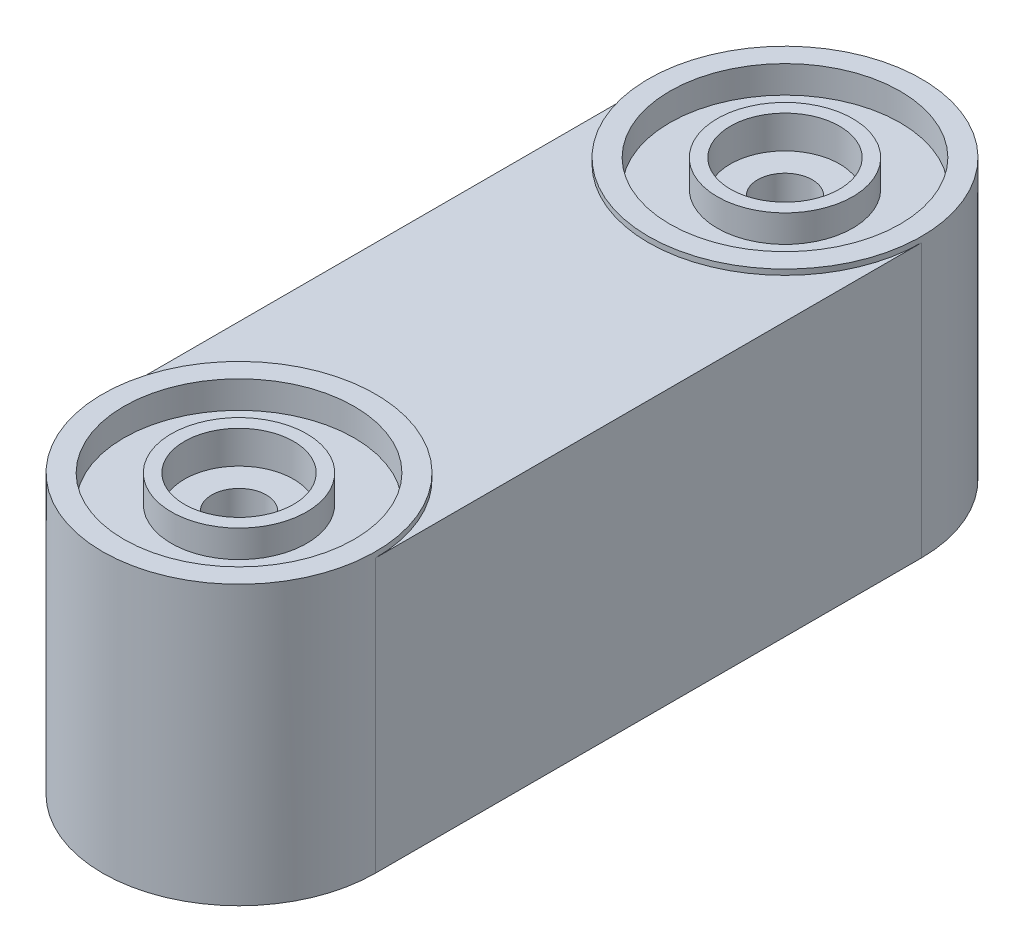
SolidWorks part; units mm, degrees
ref_plane "Ebene vorne" through (0, 0, 0) normal (0, 0, 1) x (1, 0, 0)
ref_plane "Ebene oben" through (0, 0, 0) normal (0, 1, 0) x (1, 0, 0)
ref_plane "Ebene rechts" through (0, 0, 0) normal (1, 0, 0) x (0, 0, -1)
sketch "Skizze1" plane through (0, 0, 0) normal (0, 0, 1) x (1, 0, 0)
  line L1 (-25, -25) -> (25, -25)
  line L2 (-25, -25) -> (-25, 25)
  line L3 (-25, 25) -> (25, 25)
  line L4 (25, -25) -> (25, 25)
  line L5 (-25, -25) -> (25, 25) construction
  line L6 (-25, 25) -> (25, -25) construction
  point P0 (0, 0)
  dimension "D1" = 50
  dimension "D2" = 50
extrude "Aufsatz-Linear austragen1" add sketch "Skizze1" along normal blind 150
sketch "Skizze2" plane through (0, 25, 0) normal (0, 1, 0) x (1, 0, 0)
  line L0 (25, -150) -> (25, 0) construction
  line L1 (-25, -150) -> (25, -150)
  line L2 (-25, -150) -> (-25, -100)
  line L3 (-25, -100) -> (25, -100)
  line L4 (25, -150) -> (25, -100)
  line L6 (-25, 0) -> (25, 0)
  line L7 (-25, 0) -> (-25, -50)
  line L8 (-25, -50) -> (25, -50)
  line L9 (25, 0) -> (25, -50)
  dimension "D1" = 50
  dimension "D2" = 50
extrude "Aufsatz-Linear austragen2" add sketch "Skizze2" along normal blind 1
sketch "Skizze3" plane through (0, 26, 0) normal (0, 1, 0) x (1, 0, 0)
  line L0 (-25, 0) -> (25, 0)
  line L1 (25, 0) -> (25, -50)
  line L2 (25, -50) -> (-25, -50)
  line L3 (-25, -50) -> (-25, 0)
  line L4 (-25, -100) -> (25, -100)
  line L5 (25, -100) -> (25, -150)
  line L6 (25, -150) -> (-25, -150)
  line L7 (-25, -150) -> (-25, -100)
  circle A0 centre (0, -25) radius 25
  circle A1 centre (0, -125) radius 25
  line M2 (-25, 0) -> (-25, -50)
  line M3 (-25, -50) -> (25, -50)
  line M4 (25, -50) -> (25, 0)
  line M5 (25, 0) -> (-25, 0)
extrude "Schnitt-Linear austragen1" cut sketch "Skizze3" against normal blind 1 contours A0 L0 M2 | A0 L1 M5 | A1 L6 L5 | A1 L7 L6 | A1 L4 L7 | A1 L5 L4 | A0 L3 M3 | A0 L2 M4 region at (-19.4158, 26, 5.5842) region at (19.4158, 26, 5.5842) region at (-19.4158, 26, 44.4158) region at (19.4158, 26, 44.4158) region at (-19.4158, 26, 105.5842) region at (19.4158, 26, 105.5842) region at (-19.4158, 26, 144.4158) region at (19.4158, 26, 144.4158)
sketch "Skizze4" plane through (0, 25, 0) normal (0, 1, 0) x (1, 0, 0)
  line L0 (-25, -25) -> (-25, 0)
  line L1 (-25, 0) -> (25, 0)
  line L2 (25, 0) -> (25, -25)
  line L3 (25, -25) -> (25, -125)
  line L4 (25, -125) -> (25, -150)
  line L5 (25, -150) -> (-25, -150)
  line L6 (-25, -150) -> (-25, -125)
  circle A0 centre (0, -25) radius 25
  circle A1 centre (0, -125) radius 25
  arc M1 (-25, -25) -> (0, 0) centre (0, -25) cw
  line M2 (0, 0) -> (-25, 0)
  line M3 (-25, 0) -> (-25, -25)
extrude "Schnitt-Linear austragen2" cut sketch "Skizze4" against normal blind 50 contours A1 L6 L5 | A1 L5 L4 | M3 M1 M2 | A0 L2 L1 region at (19.4158, 25, 144.4158) region at (-19.4158, 25, 5.5842) region at (19.4158, 25, 5.5842) region at (-19.4158, 25, 144.4158)
sketch "Skizze5" plane through (0, 26, 0) normal (0, 1, 0) x (1, 0, 0)
  circle A0 centre (0, -25) radius 5
  circle A1 centre (0, -125) radius 5
extrude "Schnitt-Linear austragen3" cut sketch "Skizze5" against normal blind 75
sketch "Skizze6" plane through (0, 26, 0) normal (0, 1, 0) x (1, 0, 0)
  circle A0 centre (0, -125) radius 10
  circle A1 centre (0, -25) radius 10
extrude "Schnitt-Linear austragen4" cut sketch "Skizze6" against normal blind 6
sketch "Skizze7" plane through (0, -25, 0) normal (0, -1, 0) x (1, 0, 0)
  circle A0 centre (0, 125) radius 10
  circle A1 centre (0, 25) radius 10
extrude "Schnitt-Linear austragen5" cut sketch "Skizze7" against normal blind 6
sketch "Skizze8" plane through (0, 26, 0) normal (0, 1, 0) x (1, 0, 0)
  line L0 (0, -25) -> (0, -125) construction
  line L1 (0, -75) -> (13.0656, -75) construction
  circle A0 centre (0, -25) radius 21.1
  circle A1 centre (0, -25) radius 12.4
  circle A2 centre (0, -125) radius 12.4
  circle A3 centre (0, -125) radius 21.1
  dimension "D1" = 24.8
  dimension "D2" = 42.2
extrude "Schnitt-Linear austragen6" cut sketch "Skizze8" against normal blind 5
